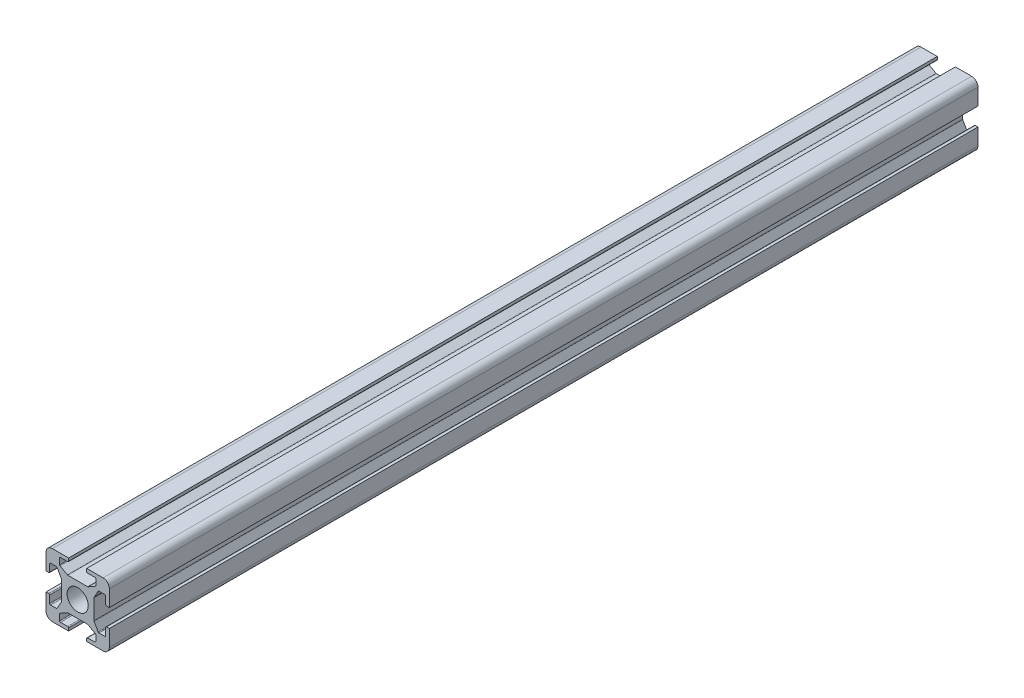
SolidWorks part; units mm, degrees
ref_plane "Alzado" through (0, 0, 0) normal (0, 0, 1) x (1, 0, 0)
ref_plane "Planta" through (0, 0, 0) normal (0, 1, 0) x (1, 0, 0)
ref_plane "Vista lateral" through (0, 0, 0) normal (1, 0, 0) x (0, 0, -1)
sketch "Croquis1" plane through (0, 0, 0) normal (0, 0, 1) x (1, 0, 0)
  line L0 (-10, 0) -> (10, 0) construction
  line L1 (0, 32.431) -> (0, -32.431) construction
  line L2 (-17.5, -5) -> (-16, -5)
  line L3 (-15.5, -15.5) -> (15.5, -15.5) construction
  line L4 (-15.5, -15.5) -> (-15.5, 15.5) construction
  line L5 (17.5, -17.5) -> (17.5, 17.5) construction
  line L6 (-17.5, -17.5) -> (17.5, 17.5) construction
  line L7 (-17.5, 17.5) -> (17.5, -17.5) construction
  line L8 (9, -9) -> (-9, -9) construction
  line L9 (9, -9) -> (9, 9) construction
  line L10 (9, 9) -> (-9, 9) construction
  line L11 (-9, -9) -> (-9, 9) construction
  line L12 (9, -9) -> (-9, 9) construction
  line L13 (9, 9) -> (-9, -9) construction
  line L14 (-15.5, 15.5) -> (15.5, 15.5) construction
  line L15 (15.5, -15.5) -> (15.5, 15.5) construction
  line L16 (-15.5, -15.5) -> (15.5, 15.5) construction
  line L17 (-15.5, 15.5) -> (15.5, -15.5) construction
  line L18 (-14.0807, -14.0828) -> (13.915, 13.9172) construction
  line L19 (-9, 15.5) -> (9, 15.5)
  line L20 (-15.5, -5.5) -> (-15.5, -9.5)
  line L21 (-15, -10) -> (-11.7901, -10)
  line L22 (-11.356, -9.7481) -> (-9.0659, -5.7407)
  line L23 (-9, -5.4926) -> (-9, 5.4926)
  line L24 (-11.356, 9.7481) -> (-9.0659, 5.7407)
  line L25 (-15, 10) -> (-11.7901, 10)
  line L26 (-15.5, 5.5) -> (-15.5, 9.5)
  line L27 (-17.5, 5) -> (-16, 5)
  line L28 (-17.5, 14) -> (-17.5, 5)
  line L29 (-17.5, -5) -> (-17.5, -14)
  line L30 (5, 17.5) -> (5, 16)
  line L31 (-17.5, 17.5) -> (17.5, 17.5) construction
  line L32 (5.5, 15.5) -> (9.5, 15.5)
  line L33 (10, 15) -> (10, 11.7901)
  line L34 (-17.5, -17.5) -> (17.5, -17.5) construction
  line L35 (9.7481, 11.356) -> (5.7407, 9.0659)
  line L36 (-17.5, -17.5) -> (-17.5, 17.5) construction
  line L37 (-17.5, 17.5) -> (17.5, 17.5) construction
  line L38 (17.5, -17.5) -> (17.5, 17.5) construction
  line L39 (-17.5, -17.5) -> (17.5, 17.5) construction
  line L40 (-17.5, 17.5) -> (17.5, -17.5) construction
  line L41 (-5.4926, 9) -> (5.4926, 9)
  line L42 (-9.7481, 11.356) -> (-5.7407, 9.0659)
  line L43 (-10, 15) -> (-10, 11.7901)
  line L44 (-10, -10) -> (10, 10) construction
  line L45 (-10, 10) -> (10, -10) construction
  line L46 (-5.5, 15.5) -> (-9.5, 15.5)
  line L47 (-5, 17.5) -> (-5, 16)
  line L48 (-14, -14) -> (14, 14) construction
  line L49 (-14, 14) -> (14, -14) construction
  line L50 (17.5, -5) -> (16, -5)
  line L51 (15.5, -5.5) -> (15.5, -9.5)
  line L52 (15, -10) -> (11.7901, -10)
  line L53 (11.356, -9.7481) -> (9.0659, -5.7407)
  line L54 (9, 5.4926) -> (9, -5.4926)
  line L55 (11.356, 9.7481) -> (9.0659, 5.7407)
  line L56 (15, 10) -> (11.7901, 10)
  line L57 (15.5, 5.5) -> (15.5, 9.5)
  line L58 (17.5, 5) -> (16, 5)
  line L59 (-5, -17.5) -> (-5, -16)
  line L60 (-5.5, -15.5) -> (-9.5, -15.5)
  line L61 (-10, -15) -> (-10, -11.7901)
  line L62 (-9.7481, -11.356) -> (-5.7407, -9.0659)
  line L63 (5.4926, -9) -> (-5.4926, -9)
  line L64 (9.7481, -11.356) -> (5.7407, -9.0659)
  line L65 (10, -15) -> (10, -11.7901)
  line L66 (5.5, -15.5) -> (9.5, -15.5)
  line L67 (5, -17.5) -> (5, -16)
  line L68 (-5, 17.5) -> (-14, 17.5)
  line L69 (5, 17.5) -> (14, 17.5)
  line L70 (17.5, 14) -> (17.5, 5)
  line L71 (17.5, -5) -> (17.5, -14)
  line L72 (14, -17.5) -> (5, -17.5)
  line L73 (-14, -17.5) -> (-5, -17.5)
  circle A0 centre (0, 0) radius 5.85
  arc A1 (-9.0659, -5.7407) -> (-9, -5.4926) centre (-9.5, -5.4926) ccw
  arc A2 (-11.7901, -10) -> (-11.356, -9.7481) centre (-11.7901, -9.5) ccw
  arc A3 (-15.5, -9.5) -> (-15, -10) centre (-15, -9.5) ccw
  arc A4 (-16, -5) -> (-15.5, -5.5) centre (-16, -5.5) cw
  arc A5 (-11.7901, 10) -> (-11.356, 9.7481) centre (-11.7901, 9.5) cw
  arc A6 (-15.5, 9.5) -> (-15, 10) centre (-15, 9.5) cw
  arc A7 (-16, 5) -> (-15.5, 5.5) centre (-16, 5.5) ccw
  arc A8 (-9.0659, 5.7407) -> (-9, 5.4926) centre (-9.5, 5.4926) cw
  arc A9 (5, 16) -> (5.5, 15.5) centre (5.5, 16) ccw
  arc A10 (9.5, 15.5) -> (10, 15) centre (9.5, 15) cw
  arc A11 (10, 11.7901) -> (9.7481, 11.356) centre (9.5, 11.7901) cw
  arc A12 (5.7407, 9.0659) -> (5.4926, 9) centre (5.4926, 9.5) cw
  arc A13 (-5.7407, 9.0659) -> (-5.4926, 9) centre (-5.4926, 9.5) ccw
  arc A14 (-10, 11.7901) -> (-9.7481, 11.356) centre (-9.5, 11.7901) ccw
  arc A15 (-9.5, 15.5) -> (-10, 15) centre (-9.5, 15) ccw
  arc A16 (-5, 16) -> (-5.5, 15.5) centre (-5.5, 16) cw
  arc A17 (16, -5) -> (15.5, -5.5) centre (16, -5.5) ccw
  arc A18 (15.5, -9.5) -> (15, -10) centre (15, -9.5) cw
  arc A19 (11.7901, -10) -> (11.356, -9.7481) centre (11.7901, -9.5) cw
  arc A20 (9.0659, -5.7407) -> (9, -5.4926) centre (9.5, -5.4926) cw
  arc A21 (9.0659, 5.7407) -> (9, 5.4926) centre (9.5, 5.4926) ccw
  arc A22 (11.7901, 10) -> (11.356, 9.7481) centre (11.7901, 9.5) ccw
  arc A23 (15.5, 9.5) -> (15, 10) centre (15, 9.5) ccw
  arc A24 (16, 5) -> (15.5, 5.5) centre (16, 5.5) cw
  arc A25 (-5, -16) -> (-5.5, -15.5) centre (-5.5, -16) ccw
  arc A26 (-9.5, -15.5) -> (-10, -15) centre (-9.5, -15) cw
  arc A27 (-10, -11.7901) -> (-9.7481, -11.356) centre (-9.5, -11.7901) cw
  arc A28 (-5.7407, -9.0659) -> (-5.4926, -9) centre (-5.4926, -9.5) cw
  arc A29 (5.7407, -9.0659) -> (5.4926, -9) centre (5.4926, -9.5) ccw
  arc A30 (10, -11.7901) -> (9.7481, -11.356) centre (9.5, -11.7901) ccw
  arc A31 (9.5, -15.5) -> (10, -15) centre (9.5, -15) ccw
  arc A32 (5, -16) -> (5.5, -15.5) centre (5.5, -16) cw
  arc A33 (17.5, -14) -> (14, -17.5) centre (14, -14) cw
  arc A34 (14, 17.5) -> (17.5, 14) centre (14, 14) cw
  arc A35 (-14, 17.5) -> (-17.5, 14) centre (-14, 14) ccw
  arc A36 (-17.5, -14) -> (-14, -17.5) centre (-14, -14) ccw
  point P0 (0, 0)
  point P4 (0, 0)
  point P31 (0, 0)
  point P37 (-11.5, -10)
  point P48 (-15.5, -10)
  point P50 (0, -15.5)
  point P53 (-9, 0)
  point P56 (0, 15.5172)
  point P149 (0, 0)
  dimension "D3" = 11.7
  dimension "D11" = 0.5
  dimension "D12" = 4
  dimension "D13" = 3.5
  dimension "D14" = 3.5
  dimension "D1" = 35
  dimension "D2" = 35
  dimension "D4" = 18
  dimension "D5" = 18
  dimension "D6" = 31
  dimension "D7" = 10
  dimension "D8" = 20
  dimension "D9" = 4
  dimension "D10" = 35
extrude "Saliente-Extruir1" add sketch "Croquis1" along normal blind 480 contours L29 A36 L73 L59 A25 L60 A26 L61 A27 L62 A28 L63 A29 L64 A30 L65 A31 L66 A32 L67 L72 A33 L71 L50 A17 L51 A18 L52 A19 L53 A20 L54 A21 L55 A22 L56 A23 L57 A24 L58 L70 A34 L69 L30 A9 L19 L32 A10 L33 A11 L35 region at (-16.75, -5.495, 0)
